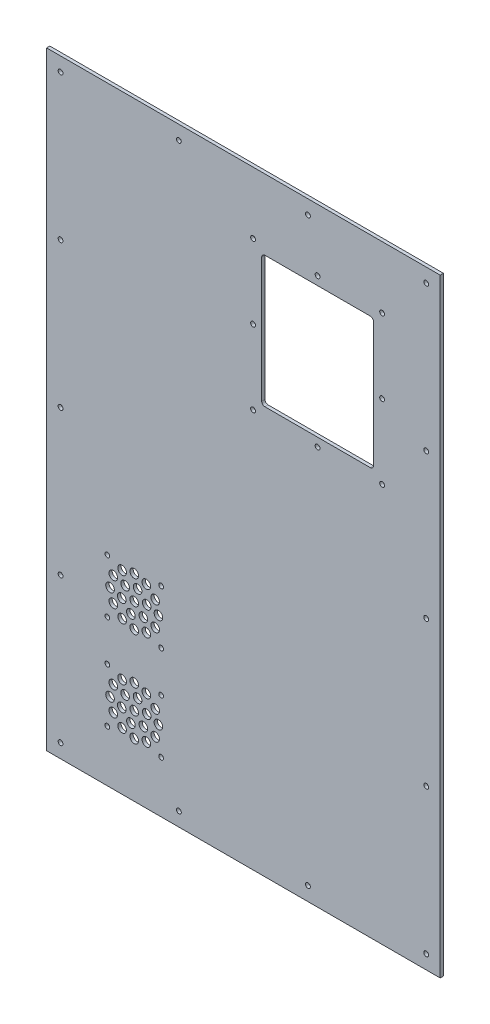
SolidWorks part; units mm, degrees
ref_plane "Спереди" through (0, 0, 0) normal (0, 0, 1) x (1, 0, 0)
ref_plane "Сверху" through (0, 0, 0) normal (0, 1, 0) x (1, 0, 0)
ref_plane "Справа" through (0, 0, 0) normal (1, 0, 0) x (0, 0, -1)
sketch "Эскиз1" plane through (0, 0, 0) normal (0, 0, 1) x (1, 0, 0)
  line L0 (0, 0) -> (366, 0)
  line L1 (0, 0) -> (0, 566)
  line L2 (366, 0) -> (366, 566)
  line L3 (0, 566) -> (366, 566)
  dimension "D1" = 566
  dimension "D2" = 366
extrude "Бобышка-Вытянуть1" add sketch "Эскиз1" along normal blind 3
sketch "Эскиз2" plane through (0, 0, 3) normal (0, 0, 1) x (1, 0, 0)
  line L0 (3, 563) -> (363, 563) construction
  line L1 (3, 563) -> (3, 3) construction
  line L2 (363, 563) -> (363, 3) construction
  line L3 (3, 3) -> (363, 3) construction
  line L4 (0, 566) -> (0, 0) construction
  line L5 (0, 0) -> (366, 0) construction
  dimension "D1" = 560
  dimension "D2" = 360
  dimension "D3" = 3
  dimension "D4" = 3
sketch "Эскиз5" plane through (0, 0, 0) normal (0, 0, -1) x (-1, 0, 0)
  line L0 (-353, 553) -> (-13, 553) construction
  line L1 (-353, 553) -> (-353, 13) construction
  line L2 (-13, 553) -> (-13, 13) construction
  line L3 (-353, 13) -> (-13, 13) construction
  line L4 (-366, 566) -> (0, 566) construction
  line L5 (-366, 0) -> (-366, 566) construction
  line L6 (0, 566) -> (0, 0) construction
  line L7 (0, 0) -> (-366, 0) construction
  line L8 (-366, 23) -> (-343, 23) construction
  line L9 (-366, 23) -> (-366, 0) construction
  line L10 (-343, 23) -> (-343, 0) construction
  line L11 (-366, 0) -> (-343, 0) construction
  line L12 (0, 0) -> (0, 23) construction
  line L13 (0, 0) -> (-23, 0) construction
  line L14 (0, 23) -> (-23, 23) construction
  line L15 (-23, 0) -> (-23, 23) construction
  line L16 (-366, 566) -> (-343, 566) construction
  line L17 (-366, 566) -> (-366, 543) construction
  line L18 (-343, 566) -> (-343, 543) construction
  line L19 (-366, 543) -> (-343, 543) construction
  line L20 (0, 566) -> (0, 543) construction
  line L21 (0, 566) -> (-23, 566) construction
  line L22 (0, 543) -> (-23, 543) construction
  line L23 (-23, 566) -> (-23, 543) construction
  line L24 (-13, 283) -> (-353, 283) construction
  line L25 (-183, 553) -> (-183, 13) construction
  circle A0 centre (-353, 553) radius 2.25
  circle A1 centre (-13, 553) radius 2.25
  circle A3 centre (-243, 553) radius 2.25
  circle A4 centre (-123, 553) radius 2.25
  circle A5 centre (-353, 418) radius 2.25
  circle A6 centre (-353, 283) radius 2.25
  circle A7 centre (-353, 148) radius 2.25
  circle A8 centre (-353, 13) radius 2.25
  circle A11 centre (-13, 418) radius 2.25
  circle A12 centre (-13, 283) radius 2.25
  circle A13 centre (-13, 148) radius 2.25
  circle A14 centre (-13, 13) radius 2.25
  circle A18 centre (-123, 13) radius 2.25
  circle A19 centre (-243, 13) radius 2.25
  dimension "D13" = 4.5
  dimension "D14" = 4.5
  dimension "D15" = 110
  dimension "D17" = 4.5
  dimension "D18" = 4.5
  dimension "D19" = 110
  dimension "D22" = 135
  dimension "D23" = 135
  dimension "D24" = 110
  dimension "D25" = 5
  dimension "D26" = 135
  dimension "D27" = 110
  dimension "D29" = 4.5
  dimension "D31" = 4.5
  dimension "D1" = 13
  dimension "D2" = 13
  dimension "D3" = 13
  dimension "D4" = 13
  dimension "D5" = 23
  dimension "D6" = 23
  dimension "D7" = 23
  dimension "D8" = 23
  dimension "D9" = 23
  dimension "D10" = 23
  dimension "D11" = 23
  dimension "D12" = 23
  dimension "D21" = 5
extrude "Вырез-Вытянуть2" cut sketch "Эскиз5" against normal through all
sketch "Эскиз6" plane through (0, 0, 3) normal (0, 0, 1) x (1, 0, 0)
  line L0 (200, 378.5) -> (200, 500.5) construction
  line L1 (200, 378.5) -> (200, 500.5)
  line L2 (200, 500.5) -> (304, 500.5) construction
  line L3 (200, 500.5) -> (304, 500.5)
  line L4 (304, 500.5) -> (304, 378.5) construction
  line L5 (304, 500.5) -> (304, 378.5)
  line L6 (304, 378.5) -> (200, 378.5) construction
  line L7 (304, 378.5) -> (200, 378.5)
extrude "Вырез-Вытянуть3" cut sketch "Эскиз6" against normal through all
sketch "Эскиз7" plane through (0, 0, 3) normal (0, 0, 1) x (1, 0, 0)
  circle A0 centre (192, 370.5) radius 2.25 construction
  circle A1 centre (192, 370.5) radius 2.25
  circle A2 centre (192, 439.5) radius 2.25 construction
  circle A3 centre (192, 439.5) radius 2.25
  circle A4 centre (192, 508.5) radius 2.25 construction
  circle A5 centre (192, 508.5) radius 2.25
  circle A6 centre (252, 370.5) radius 2.25 construction
  circle A7 centre (252, 370.5) radius 2.25
  circle A8 centre (312, 370.5) radius 2.25 construction
  circle A9 centre (312, 370.5) radius 2.25
  circle A10 centre (252, 508.5) radius 2.25 construction
  circle A11 centre (252, 508.5) radius 2.25
  circle A12 centre (312, 508.5) radius 2.25 construction
  circle A13 centre (312, 508.5) radius 2.25
  circle A14 centre (312, 439.5) radius 2.25 construction
  circle A15 centre (312, 439.5) radius 2.25
  circle A16 centre (312, 370.5) radius 2.25
extrude "Вырез-Вытянуть4" cut sketch "Эскиз7" against normal through all contours A3 | A11 | A13 | A15 | A9 | A7 | A1 | A5 region at (192, 370.5, 3) region at (192, 439.5, 3) region at (252, 370.5, 3) region at (312, 370.5, 3) region at (252, 508.5, 3) region at (312, 508.5, 3) region at (312, 439.5, 3)
fillet "Fillet2" radius 3 4 edges at (200, 378.5, 1.5) (304, 378.5, 1.5) (304, 500.5, 1.5) (200, 500.5, 1.5)
sketch "Эскиз8" plane through (0, 0, 0) normal (0, 0, -1) x (-1, 0, 0)
  line L0 (-81.5, 0) -> (-81.5, 161) construction
  line L1 (0, 0) -> (-366, 0) construction
  line L2 (-81.5, 161) -> (0, 161) construction
  line L3 (0, 566) -> (0, 0) construction
  line L4 (-81.5, 73) -> (0, 73) construction
  line L5 (-81.5, 161) -> (-97.4099, 145.0901) construction
  line L6 (-81.5, 73) -> (-89.9853, 64.5147) construction
  line L7 (-284.5, 0) -> (-284.5, 111) construction
  line L8 (-106.5, 136) -> (-56.5, 136) construction
  line L9 (-106.5, 136) -> (-106.5, 186) construction
  line L10 (-106.5, 186) -> (-56.5, 186) construction
  line L11 (-56.5, 136) -> (-56.5, 186) construction
  line L12 (-106.5, 136) -> (-56.5, 186) construction
  line L13 (-106.5, 186) -> (-56.5, 136) construction
  line L14 (-106.5, 48) -> (-56.5, 48) construction
  line L15 (-106.5, 48) -> (-106.5, 98) construction
  line L16 (-106.5, 98) -> (-56.5, 98) construction
  line L17 (-56.5, 48) -> (-56.5, 98) construction
  line L18 (-106.5, 48) -> (-56.5, 98) construction
  line L19 (-106.5, 98) -> (-56.5, 48) construction
  line L20 (-284.5, 111) -> (-366, 111) construction
  line L21 (-366, 0) -> (-366, 566) construction
  line L22 (-284.5, 111) -> (-292.9853, 102.5147) construction
  line L24 (-309.5, 136) -> (-259.5, 136) construction
  line L25 (-309.5, 136) -> (-309.5, 86) construction
  line L26 (-309.5, 86) -> (-259.5, 86) construction
  line L27 (-259.5, 136) -> (-259.5, 86) construction
  line L28 (-309.5, 136) -> (-259.5, 86) construction
  line L29 (-309.5, 86) -> (-259.5, 136) construction
  circle A0 centre (-81.5, 161) radius 12 construction
  circle A1 centre (-81.5, 161) radius 22.5 construction
  circle A2 centre (-81.5, 138.5) radius 4
  circle A3 centre (-89.9853, 152.5147) radius 4
  circle A4 centre (-81.5, 161) radius 4
  circle A5 centre (-92.75, 141.5144) radius 4
  circle A6 centre (-100.9856, 149.75) radius 4
  circle A7 centre (-104, 161) radius 4
  circle A8 centre (-100.9856, 172.25) radius 4
  circle A9 centre (-92.75, 180.4856) radius 4
  circle A10 centre (-81.5, 183.5) radius 4
  circle A11 centre (-70.25, 180.4856) radius 4
  circle A12 centre (-62.0144, 172.25) radius 4
  circle A13 centre (-59, 161) radius 4
  circle A14 centre (-62.0144, 149.75) radius 4
  circle A15 centre (-70.25, 141.5144) radius 4
  circle A16 centre (-93.0911, 164.1058) radius 4
  circle A17 centre (-84.6058, 172.5911) radius 4
  circle A18 centre (-73.0147, 169.4853) radius 4
  circle A19 centre (-69.9089, 157.8942) radius 4
  circle A20 centre (-78.3942, 149.4089) radius 4
  circle A21 centre (-81.5, 73) radius 12 construction
  circle A22 centre (-81.5, 73) radius 22.5 construction
  circle A23 centre (-81.5, 73) radius 4
  circle A24 centre (-81.5, 50.5) radius 4
  circle A25 centre (-89.9853, 64.5147) radius 4
  circle A26 centre (-92.75, 53.5144) radius 4
  circle A27 centre (-100.9856, 61.75) radius 4
  circle A28 centre (-104, 73) radius 4
  circle A29 centre (-100.9856, 84.25) radius 4
  circle A30 centre (-92.75, 92.4856) radius 4
  circle A31 centre (-81.5, 95.5) radius 4
  circle A32 centre (-70.25, 92.4856) radius 4
  circle A33 centre (-62.0144, 84.25) radius 4
  circle A34 centre (-59, 73) radius 4
  circle A35 centre (-62.0144, 61.75) radius 4
  circle A36 centre (-70.25, 53.5144) radius 4
  circle A37 centre (-93.0911, 76.1058) radius 4
  circle A38 centre (-84.6058, 84.5911) radius 4
  circle A39 centre (-73.0147, 81.4853) radius 4
  circle A40 centre (-69.9089, 69.8942) radius 4
  circle A41 centre (-78.3942, 61.4089) radius 4
  circle A42 centre (-106.5, 186) radius 2.2
  circle A43 centre (-56.5, 186) radius 2.2
  circle A44 centre (-56.5, 136) radius 2.2
  circle A45 centre (-106.5, 136) radius 2.2
  circle A46 centre (-56.5, 98) radius 2.2
  circle A47 centre (-56.5, 48) radius 2.2
  circle A48 centre (-106.5, 48) radius 2.2
  circle A49 centre (-106.5, 98) radius 2.2
  circle A50 centre (-284.5, 111) radius 12 construction
  circle A51 centre (-284.5, 111) radius 22.5 construction
  circle A52 centre (-284.5, 111) radius 4 construction
  circle A53 centre (-284.5, 88.5) radius 4 construction
  circle A54 centre (-292.9853, 102.5147) radius 4 construction
  circle A55 centre (-295.75, 91.5144) radius 4 construction
  circle A56 centre (-303.9856, 99.75) radius 4 construction
  circle A57 centre (-307, 111) radius 4 construction
  circle A58 centre (-303.9856, 122.25) radius 4 construction
  circle A59 centre (-295.75, 130.4856) radius 4 construction
  circle A60 centre (-284.5, 133.5) radius 4 construction
  circle A61 centre (-273.25, 130.4856) radius 4 construction
  circle A62 centre (-265.0144, 122.25) radius 4 construction
  circle A63 centre (-262, 111) radius 4 construction
  circle A64 centre (-265.0144, 99.75) radius 4 construction
  circle A65 centre (-273.25, 91.5144) radius 4 construction
  circle A66 centre (-296.0911, 114.1058) radius 4 construction
  circle A67 centre (-287.6058, 122.5911) radius 4 construction
  circle A68 centre (-276.0147, 119.4853) radius 4 construction
  circle A69 centre (-272.9089, 107.8942) radius 4 construction
  circle A70 centre (-281.3942, 99.4089) radius 4 construction
  circle A71 centre (-309.5, 136) radius 2.2 construction
  circle A72 centre (-259.5, 136) radius 2.2 construction
  circle A73 centre (-259.5, 86) radius 2.2 construction
  circle A74 centre (-309.5, 86) radius 2.2 construction
  point P26 (-81.5, 161)
  point P52 (-81.5, 161)
  point P82 (-81.5, 73)
  point P93 (-81.5, 73)
  point P144 (-284.5, 111)
  point P155 (-284.5, 111)
  dimension "D4" = 45
  dimension "D5" = 24
  dimension "D7" = 8
  dimension "D8" = 8
  dimension "D9" = 8
  dimension "D12" = 8
  dimension "D13" = 8
  dimension "D14" = 8
  dimension "D16" = 24
  dimension "D17" = 45
  dimension "D22" = 4.4
  dimension "D25" = 4.4
  dimension "D28" = 24
  dimension "D29" = 45
  dimension "D30" = 8
  dimension "D31" = 45
  dimension "D36" = 4.4
  dimension "D1" = 73
  dimension "D2" = 161
  dimension "D3" = 81.5
  dimension "D6" = 45
  dimension "D15" = 45
  dimension "D20" = 50
  dimension "D21" = 50
  dimension "D23" = 50
  dimension "D24" = 50
  dimension "D26" = 81.5
  dimension "D27" = 111
  dimension "D34" = 50
  dimension "D35" = 50
  dimension "D10" = 12
  dimension "D11" = 6
  dimension "D18" = 12
  dimension "D19" = 6
  dimension "D32" = 12
  dimension "D33" = 6
extrude "Вырез-Вытянуть5" cut sketch "Эскиз8" against normal through all
